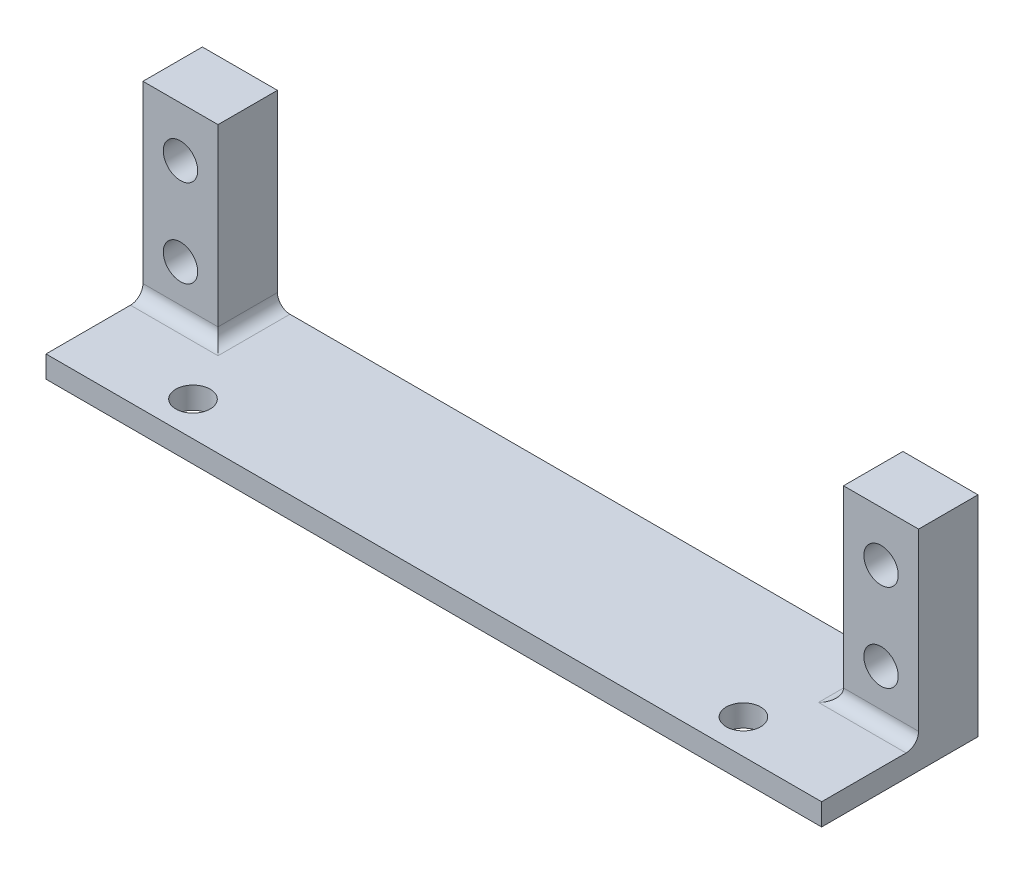
SolidWorks part; units mm, degrees
ref_plane "Front" through (0, 0, 0) normal (0, 0, 1) x (1, 0, 0)
ref_plane "Top" through (0, 0, 0) normal (0, 1, 0) x (1, 0, 0)
ref_plane "Right" through (0, 0, 0) normal (1, 0, 0) x (0, 0, -1)
sketch "Sketch1" plane through (0, 0, 0) normal (0, 1, 0) x (1, 0, 0)
  line L1 (0, 0) -> (50, 0)
  line L2 (0, 0) -> (0, 12.5)
  line L3 (0, 12.5) -> (50, 12.5)
  line L4 (50, 0) -> (50, 12.5)
  dimension "D1" = 50
  dimension "D2" = 12.5
extrude "base" add sketch "Sketch1" along normal blind 1.75
sketch "Sketch2" plane through (0, 1.75, 0) normal (0, 1, 0) x (1, 0, 0)
  line L0 (25, 0) -> (25, 12.5) construction
  line L1 (0, 0) -> (50, 0) construction
  line L2 (50, 12.5) -> (0, 12.5) construction
  line L3 (0, 12.5) -> (0, 0) construction
  circle A0 centre (3, 2.75) radius 1.375
  circle A1 centre (47, 2.75) radius 1.375
  dimension "D1" = 2.75
  dimension "D2" = 2.75
  dimension "D3" = 3
extrude "chassisMountingHoles" cut sketch "Sketch2" against normal blind 1.75
sketch "Sketch3" plane through (0, 0, -12.5) normal (0, 0, -1) x (-1, 0, 0)
  line L0 (0, 1.75) -> (6, 1.75) construction
  line L1 (0, 0) -> (6, 0)
  line L2 (0, 0) -> (0, 16.75)
  line L3 (0, 16.75) -> (6, 16.75)
  line L4 (6, 0) -> (6, 16.75)
  line L5 (3, 12.75) -> (3, 5.75) construction
  line L6 (-25, 1.75) -> (-25, 16.75) construction
  line L8 (-50, 1.75) -> (0, 1.75) construction
  line L9 (-50, 0) -> (-56, 0)
  line L10 (-50, 16.75) -> (-56, 16.75)
  line L11 (-50, 0) -> (-50, 16.75)
  line L12 (-56, 0) -> (-56, 16.75)
  circle A0 centre (3, 12.75) radius 2.3 construction
  circle A1 centre (3, 5.75) radius 2.3 construction
  circle A2 centre (3, 12.75) radius 1.375
  circle A3 centre (3, 5.75) radius 1.375
  circle A4 centre (-53, 12.75) radius 1.375
  circle A5 centre (-53, 5.75) radius 1.375
  point P10 (3, 16.75)
  point P17 (3, 9.25)
  point P18 (-25, 9.25)
  dimension "D3" = 4.6
  dimension "D5" = 2.75
  dimension "D1" = 6
  dimension "D2" = 15
  dimension "D4" = 7
extrude "Boss-Extrude2" add sketch "Sketch3" against normal blind 1.75
sketch "Sketch4" plane through (0, 1.75, 0) normal (0, 1, 0) x (1, 0, 0)
  line L0 (25, 0) -> (25, 12.5) construction
  line L1 (0, 0) -> (50, 0) construction
  line L2 (50, 12.5) -> (0, 12.5) construction
  line L3 (50, 0) -> (56, 10.75)
  line L4 (56, 10.75) -> (50, 10.75)
  line L5 (50, 10.75) -> (50, 0)
  line L6 (-6, 10.75) -> (0, 10.75)
  line L7 (0, 0) -> (-6, 10.75)
  line L8 (0, 10.75) -> (0, 0)
extrude "Boss-Extrude3" add sketch "Sketch4" against normal up to surface (1.75 mm away) up to face at (3, 0, -1.375)
sketch "Sketch5" plane through (0, 0, -10.75) normal (0, 0, 1) x (1, 0, 0)
  line L4 (-6, 16.75) -> (-6, 1.75)
  line L5 (-6, 1.75) -> (0, 1.75)
  line L6 (0, 1.75) -> (0, 16.75)
  line L7 (0, 16.75) -> (-6, 16.75)
  line L8 (-6, 16.75) -> (-6, 1.75)
  line L9 (-6, 1.75) -> (0, 1.75)
  line L10 (0, 1.75) -> (0, 16.75)
  line L11 (0, 16.75) -> (-6, 16.75)
  line L12 (50, 1.75) -> (56, 1.75)
  line L13 (56, 1.75) -> (56, 16.75)
  line L14 (56, 16.75) -> (50, 16.75)
  line L15 (50, 16.75) -> (50, 1.75)
  line L16 (50, 1.75) -> (56, 1.75)
  line L17 (56, 1.75) -> (56, 16.75)
  line L18 (56, 16.75) -> (50, 16.75)
  line L19 (50, 16.75) -> (50, 1.75)
  circle A0 centre (53, 5.75) radius 1.375 construction
  circle A1 centre (53, 12.75) radius 1.375 construction
  circle A2 centre (-3, 5.75) radius 1.375 construction
  circle A3 centre (-3, 12.75) radius 1.375 construction
  circle A4 centre (53, 5.75) radius 1.375
  circle A5 centre (53, 12.75) radius 1.375
  circle A6 centre (-3, 5.75) radius 1.375
  circle A7 centre (-3, 12.75) radius 1.375
  dimension "D1" = 0
  dimension "D2" = 0
extrude "Boss-Extrude4" add sketch "Sketch5" along normal blind 3
sketch "Sketch6" plane through (0, 0, 0) normal (0, -1, 0) x (1, 0, 0)
  line L0 (-6, -10.75) -> (-6, 0)
  line L1 (-6, 0) -> (0, 0)
  line L2 (0, 0) -> (-6, -10.75)
  line L3 (25, -12.5) -> (25, 0) construction
  line L4 (56, -12.5) -> (-6, -12.5) construction
  line L5 (0, 0) -> (50, 0) construction
  line L6 (56, 0) -> (50, 0)
  line L7 (56, -10.75) -> (56, 0)
  line L8 (50, 0) -> (56, -10.75)
extrude "Boss-Extrude5" add sketch "Sketch6" against normal up to surface (1.75 mm away) up to face at (-5.4419, 1.75, -8.75)
fillet "Fillet1" radius 1 4 edges at (-3, 1.75, -7.75) (50, 1.75, -10.125) (53, 1.75, -7.75) (0, 1.75, -10.125)
